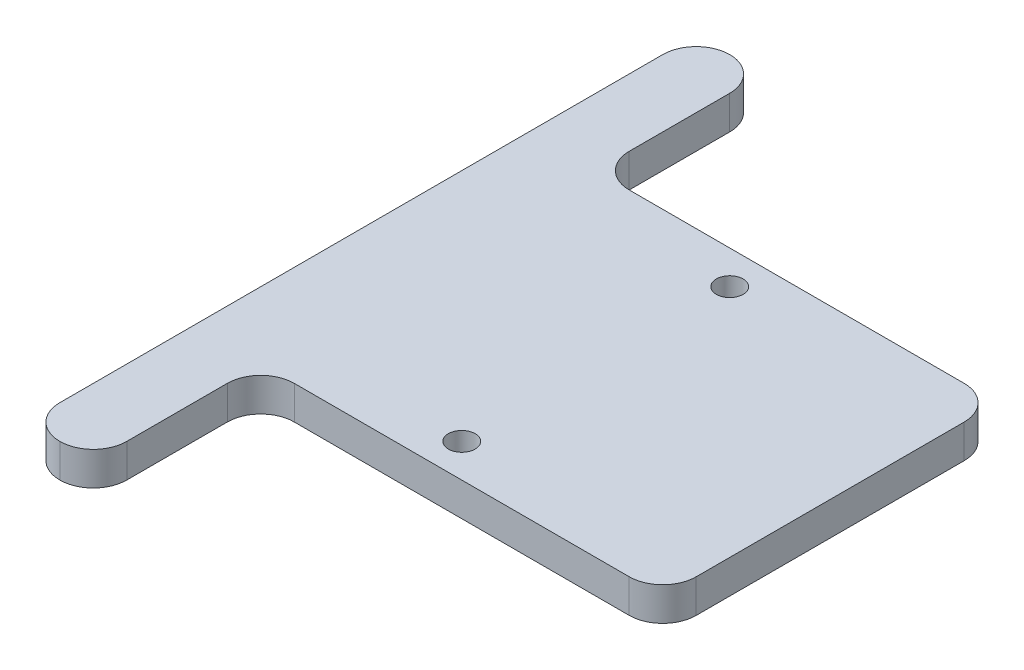
SolidWorks part; units mm, degrees
ref_plane "정면" through (0, 0, 0) normal (0, 0, 1) x (1, 0, 0)
ref_plane "윗면" through (0, 0, 0) normal (0, 1, 0) x (1, 0, 0)
ref_plane "우측면" through (0, 0, 0) normal (1, 0, 0) x (0, 0, -1)
sketch "스케치2" plane through (0, 0, 0) normal (0, 1, 0) x (1, 0, 0)
  line L0 (-60, -25) -> (-60, -50)
  line L1 (-60, 25) -> (0, 25)
  line L3 (-60, -25) -> (0, -25)
  line L4 (0, 25) -> (0, -25)
  line L5 (-60, 25) -> (0, -25) construction
  line L6 (-60, -25) -> (0, 25) construction
  line L11 (-70, 50) -> (-60, 50)
  line L12 (-70, 50) -> (-70, -50)
  line L13 (-70, -50) -> (-60, -50)
  line L14 (-60, 50) -> (-60, 25)
  line L15 (-35, 25) -> (-35, -25) construction
  line L16 (-70, 0) -> (0, 0) construction
  circle A0 centre (-35, 20) radius 2
  circle A1 centre (-35, -20) radius 2
  point P0 (-30, 0)
  point P5 (0, 0)
  point P11 (-70, 0)
  point P20 (-35, 0)
  dimension "D5" = 4
  dimension "D1" = 50
  dimension "D2" = 60
  dimension "D3" = 100
  dimension "D4" = 10
  dimension "D6" = 40
extrude "보스-돌출1" add sketch "스케치2" along normal blind 5
fillet "필렛1" radius 5 8 edges at (-60, 2.5, -25) (0, 2.5, -25) (0, 2.5, 25) (-60, 2.5, 25) (-60, 2.5, 50) (-70, 2.5, 50) (-60, 2.5, -50) (-70, 2.5, -50)
